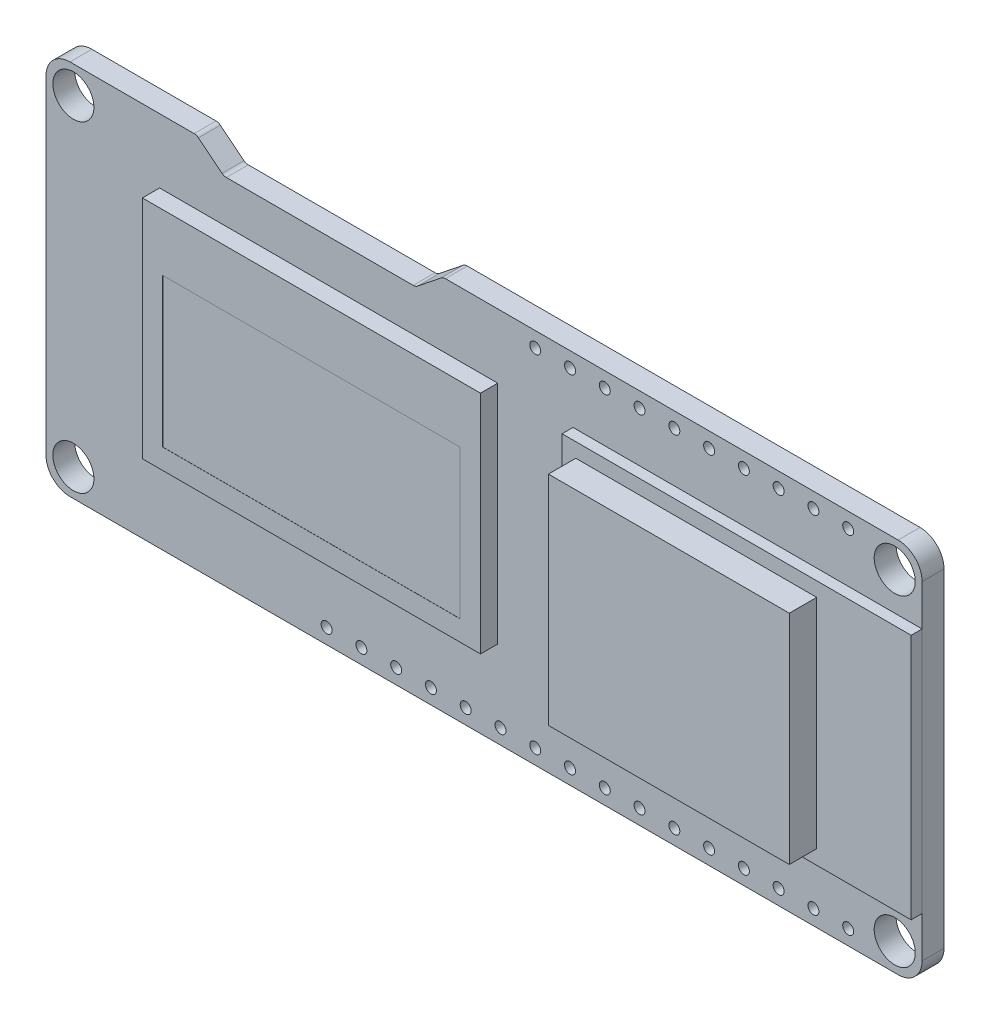
SolidWorks part; units mm, degrees
other "OLED"
other "ESP32"
other "PCB"
ref_plane "Plan de face" through (0, 0, 0) normal (0, 0, 1) x (1, 0, 0)
ref_plane "Plan de dessus" through (0, 0, 0) normal (0, 1, 0) x (1, 0, 0)
ref_plane "Plan de droite" through (0, 0, 0) normal (1, 0, 0) x (0, 0, -1)
sketch "Esquisse1" plane through (0, 0, 0) normal (0, 0, 1) x (1, 0, 0)
  line L0 (-20.863, 13.6404) -> (-19.137, 12.2596)
  line L1 (-30.25, -13.75) -> (30.25, -13.75)
  line L2 (-32, -12) -> (-32, 12)
  line L3 (-30.25, 13.75) -> (-21.1754, 13.75)
  line L4 (32, -12) -> (32, 12)
  line L5 (-32, -13.75) -> (32, 13.75) construction
  line L6 (-32, 13.75) -> (32, -13.75) construction
  line L7 (-30, -11.75) -> (30, -11.75) construction
  line L8 (-30, -11.75) -> (-30, 11.75) construction
  line L9 (-30, 11.75) -> (30, 11.75) construction
  line L10 (30, -11.75) -> (30, 11.75) construction
  line L11 (-30, -11.75) -> (30, 11.75) construction
  line L12 (-30, 11.75) -> (30, -11.75) construction
  line L13 (-18.8246, 12.15) -> (-5.1754, 12.15)
  line L14 (-4.863, 12.2596) -> (-3.137, 13.6404)
  line L15 (-21, 13.75) -> (-3, 13.75) construction
  line L16 (-2.8246, 13.75) -> (30.25, 13.75)
  line L17 (32, 0) -> (0, 0) construction
  arc A0 (30.25, -13.75) -> (32, -12) centre (30.25, -12) ccw
  arc A1 (-30.25, -13.75) -> (-32, -12) centre (-30.25, -12) cw
  arc A2 (-32, 12) -> (-30.25, 13.75) centre (-30.25, 12) cw
  arc A3 (30.25, 13.75) -> (32, 12) centre (30.25, 12) cw
  circle A4 centre (30, 11.75) radius 1.5
  circle A5 centre (30, -11.75) radius 1.5
  circle A6 centre (-30, -11.75) radius 1.5
  circle A7 centre (-30, 11.75) radius 1.5
  arc A8 (-2.8246, 13.75) -> (-3.137, 13.6404) centre (-2.8246, 13.25) ccw
  arc A9 (-4.863, 12.2596) -> (-5.1754, 12.15) centre (-5.1754, 12.65) cw
  arc A10 (-19.137, 12.2596) -> (-18.8246, 12.15) centre (-18.8246, 12.65) ccw
  arc A11 (-20.863, 13.6404) -> (-21.1754, 13.75) centre (-21.1754, 13.25) ccw
  circle A12 centre (26.6, 12.65) radius 0.4
  circle A13 centre (24.06, 12.65) radius 0.4
  circle A14 centre (21.52, 12.65) radius 0.4
  circle A15 centre (18.98, 12.65) radius 0.4
  circle A16 centre (16.44, 12.65) radius 0.4
  circle A17 centre (13.9, 12.65) radius 0.4
  circle A18 centre (11.36, 12.65) radius 0.4
  circle A19 centre (8.82, 12.65) radius 0.4
  circle A20 centre (6.28, 12.65) radius 0.4
  circle A21 centre (3.74, 12.65) radius 0.4
  circle A22 centre (26.6, -12.65) radius 0.4
  circle A23 centre (24.06, -12.65) radius 0.4
  circle A24 centre (21.52, -12.65) radius 0.4
  circle A25 centre (18.98, -12.65) radius 0.4
  circle A26 centre (16.44, -12.65) radius 0.4
  circle A27 centre (13.9, -12.65) radius 0.4
  circle A28 centre (11.36, -12.65) radius 0.4
  circle A29 centre (8.82, -12.65) radius 0.4
  circle A30 centre (6.28, -12.65) radius 0.4
  circle A31 centre (3.74, -12.65) radius 0.4
  circle A32 centre (1.2, -12.65) radius 0.4
  circle A33 centre (-1.34, -12.65) radius 0.4
  circle A34 centre (-3.88, -12.65) radius 0.4
  circle A35 centre (-6.42, -12.65) radius 0.4
  circle A36 centre (-8.96, -12.65) radius 0.4
  circle A37 centre (-11.5, -12.65) radius 0.4
  point P0 (0, 0)
  point P18 (0, 0)
  point P27 (-19, 13.75)
  point P28 (-5, 13.75)
  point P29 (-21, 13.75)
  point P30 (-3, 13.75)
  point P31 (-19, 12.15)
  point P33 (-5, 12.15)
  point P42 (-5, 12.15)
  point P45 (-19, 12.15)
  dimension "D3" = 1.75
  dimension "D6" = 3
  dimension "D12" = 0.5
  dimension "D13" = 5.4
  dimension "D15" = 0.8
  dimension "D1" = 27.5
  dimension "D2" = 64
  dimension "D4" = 2
  dimension "D5" = 2
  dimension "D7" = 13
  dimension "D8" = 2
  dimension "D9" = 2
  dimension "D10" = 14
  dimension "D11" = 1.6
  dimension "D14" = 1.1
  dimension "D17" = 16
  dimension "D16" = 10
extrude "Boss.-Extru.1" add sketch "Esquisse1" against normal blind 1.6
sketch "Esquisse2" plane through (0, 0, 0) normal (0, 0, 1) x (1, 0, 0)
  line L0 (32, -12) -> (32, 12) construction
  line L1 (32, 9) -> (6.5, 9)
  line L2 (32, 9) -> (32, -9)
  line L3 (32, -9) -> (6.5, -9)
  line L4 (6.5, 9) -> (6.5, -9)
  point P7 (32, 0)
  dimension "D1" = 18
  dimension "D2" = 25.5
extrude "Boss.-Extru.2" add sketch "Esquisse2" along normal blind 0.8 separate body
sketch "Esquisse3" plane through (0, 0, 0.8) normal (0, 0, 1) x (1, 0, 0)
  line L0 (6.5, 9) -> (6.5, -9) construction
  line L1 (7.5, 7.95) -> (25.1, 7.95)
  line L2 (7.5, 7.95) -> (7.5, -7.95)
  line L3 (7.5, -7.95) -> (25.1, -7.95)
  line L4 (25.1, 7.95) -> (25.1, -7.95)
  line L5 (6.5, 0) -> (7.5, 0) construction
  point P6 (6.5, 0)
  dimension "D1" = 1
  dimension "D2" = 15.9
  dimension "D3" = 17.6
extrude "Boss.-Extru.3" add sketch "Esquisse3" along normal blind 2
sketch "Esquisse4" plane through (0, 0, 0) normal (0, 0, 1) x (1, 0, 0)
  line L0 (-32, 12) -> (-32, -12) construction
  line L1 (-23.7, 9.05) -> (1, 9.05)
  line L2 (-23.7, 9.05) -> (-23.7, -7.45)
  line L3 (-23.7, -7.45) -> (1, -7.45)
  line L4 (1, 9.05) -> (1, -7.45)
  line L6 (-21.1754, 13.75) -> (-30.25, 13.75) construction
  dimension "D1" = 16.5
  dimension "D2" = 24.7
  dimension "D3" = 4.7
  dimension "D4" = 8.3
extrude "Boss.-Extru.4" add sketch "Esquisse4" along normal blind 1.26 separate body
sketch "Esquisse5" plane through (0, 0, 1.26) normal (0, 0, 1) x (1, 0, 0)
  line L0 (-22.22, 4.89) -> (-23.7, 4.89) construction
  line L1 (-22.22, 4.89) -> (-0.48, 4.89)
  line L2 (-22.22, 4.89) -> (-22.22, -5.97)
  line L3 (-22.22, -5.97) -> (-0.48, -5.97)
  line L4 (-0.48, 4.89) -> (-0.48, -5.97)
  line L5 (-23.7, 9.05) -> (-23.7, -7.45) construction
  line L6 (-22.22, -5.97) -> (-22.22, -7.45) construction
  line L8 (-0.48, 4.89) -> (1, 4.89) construction
  line L9 (1, -7.45) -> (1, 9.05) construction
  line L10 (-23.7, -7.45) -> (1, -7.45) construction
  dimension "D1" = 21.74
  dimension "D2" = 10.86
extrude "Enlèv. mat.-Extru.1" cut sketch "Esquisse5" against normal blind 0.1
other "Déplacer la face2" face at (-11.35, -0.54, 1.16) offset 0.09 parameters "D1"=0.09
sketch "Esquisse7" plane through (0, 0, -1.6) normal (0, 0, -1) x (-1, 0, 0)
  line L0 (32, 12) -> (32, -12) construction
  line L1 (32, -8.55) -> (26.2, -8.55)
  line L2 (32, -8.55) -> (32, -0.55)
  line L3 (32, -0.55) -> (26.2, -0.55)
  line L4 (26.2, -8.55) -> (26.2, -0.55)
  line L5 (30.25, -13.75) -> (-30.25, -13.75) construction
  point P6 (26.2, -4.55)
  dimension "D1" = 8
  dimension "D2" = 5.8
  dimension "D3" = 5.2
extrude "Boss.-Extru.5" add sketch "Esquisse7" along normal blind 2.6
sketch "Esquisse8" plane through (-32, 0, 0) normal (-1, 0, 0) x (0, 0, 1)
  line L0 (-4.2, -8.55) -> (-1.6, -8.55) construction
  line L1 (-4.2, -0.55) -> (-1.4, -0.55)
  line L2 (-4.2, -0.55) -> (-4.2, -8.55)
  line L3 (-4.2, -8.55) -> (-1.4, -8.55)
  line L4 (-1.4, -0.55) -> (-1.4, -8.55)
  dimension "D1" = 2.8
extrude "Boss.-Extru.6" add sketch "Esquisse8" along normal blind 0.8
fillet "Congé1" radius 0.66 2 edges at (-29.5, -0.55, -4.2) (-29.5, -8.55, -4.2)
chamfer "Chanfrein1" distance 1 angle 45 2 edges at (-32.4, -0.55, -1.4) (-32.4, -8.55, -1.4)
sketch "Esquisse9" plane through (-32.8, 0, 0) normal (-1, 0, 0) x (0, 0, 1)
  line L6 (-3.05, -4.55) -> (-3.87, -4.55) construction
  line L7 (-3.05, -2.55) -> (-2.55, -2.55)
  line L8 (-3.05, -2.55) -> (-3.05, -6.55)
  line L9 (-3.05, -6.55) -> (-2.55, -6.55)
  line L10 (-2.55, -2.55) -> (-2.55, -6.55)
  line L11 (-2.55, -4.55) -> (-1.73, -4.55) construction
  line L12 (-1.73, -7.4133) -> (-1.73, -1.6867)
  line L13 (-1.73, -1.6867) -> (-2.5367, -0.88)
  line L14 (-2.5367, -0.88) -> (-3.54, -0.88)
  line L15 (-3.87, -1.21) -> (-3.87, -7.89)
  line L16 (-3.54, -8.22) -> (-2.5367, -8.22)
  line L17 (-2.5367, -8.22) -> (-1.73, -7.4133)
  line L18 (-1.73, -7.4133) -> (-1.73, -1.6867)
  line L19 (-1.73, -1.6867) -> (-2.5367, -0.88)
  line L20 (-2.5367, -0.88) -> (-3.54, -0.88)
  line L21 (-3.87, -1.21) -> (-3.87, -7.89)
  line L22 (-3.54, -8.22) -> (-2.5367, -8.22)
  line L23 (-2.5367, -8.22) -> (-1.73, -7.4133)
  arc A4 (-3.54, -0.88) -> (-3.87, -1.21) centre (-3.54, -1.21) ccw
  arc A5 (-3.87, -7.89) -> (-3.54, -8.22) centre (-3.54, -7.89) ccw
  arc A6 (-3.54, -0.88) -> (-3.87, -1.21) centre (-3.54, -1.21) ccw
  arc A7 (-3.87, -7.89) -> (-3.54, -8.22) centre (-3.54, -7.89) ccw
  dimension "D2" = 0.5
  dimension "D3" = 4
  dimension "D1" = 0.33
extrude "Enlèv. mat.-Extru.2" cut sketch "Esquisse9" against normal blind 5
sketch "Esquisse10" plane through (0, 0, -1.6) normal (0, 0, -1) x (-1, 0, 0)
  line L0 (32, 12) -> (32, -1.35) construction
  line L1 (28.4, 7.55) -> (31.4, 7.55)
  line L2 (28.4, 7.55) -> (28.4, 3.55)
  line L3 (28.4, 3.55) -> (31.4, 3.55)
  line L4 (31.4, 7.55) -> (31.4, 3.55)
  line L5 (21.1754, 13.75) -> (30.25, 13.75) construction
  line L6 (24.1, 7.55) -> (24.1, 3.55)
  line L7 (24.1, 7.55) -> (27.1, 7.55)
  line L8 (27.1, 7.55) -> (27.1, 3.55)
  line L9 (24.1, 3.55) -> (27.1, 3.55)
  dimension "D1" = 4
  dimension "D2" = 3
  dimension "D3" = 0.6
  dimension "D4" = 6.2
  dimension "D5" = 2
extrude "Boss.-Extru.7" add sketch "Esquisse10" along normal blind 1.8
sketch "Esquisse11" plane through (0, 0, -3.4) normal (0, 0, -1) x (-1, 0, 0)
  line L0 (31.4, 7.55) -> (28.4, 3.55) construction
  line L1 (27.1, 7.55) -> (24.1, 3.55) construction
  circle A0 centre (25.6, 5.55) radius 0.9
  circle A1 centre (29.9, 5.55) radius 0.9
  dimension "D1" = 1.8
extrude "Boss.-Extru.8" add sketch "Esquisse11" along normal blind 0.5
sketch "Esquisse12" plane through (0, 0, -1.6) normal (0, 0, -1) x (-1, 0, 0)
  line L0 (-3.5, 8.05) -> (-3.5, -11.25)
  line L2 (32, 12) -> (32, -1.35) construction
  line L3 (27.1, 7.55) -> (24.1, 7.55) construction
  line L4 (-3.5, 8.05) -> (22.7644, 8.05)
  line L5 (22.7644, 8.05) -> (22.7644, 2.05)
  line L6 (22.7644, 2.05) -> (24.4, 2.05)
  line L7 (24.4, 2.05) -> (24.4, -9.75)
  line L8 (24.4, -9.75) -> (26, -9.75)
  line L9 (26, -9.75) -> (26, -13.75)
  line L10 (30.25, -13.75) -> (-30.25, -13.75) construction
  line L11 (26, -13.75) -> (14.4, -13.75)
  line L12 (14.4, -13.75) -> (14.4, -11.25)
  line L13 (14.4, -11.25) -> (-3.5, -11.25)
  line L14 (26.2, -1.35) -> (26.2, -7.75) construction
  line L15 (32, -7.75) -> (32, -12) construction
  line L16 (-32, -12) -> (-32, 12) construction
  line L17 (-25.5, 7.05) -> (-14, 7.05)
  line L18 (-25.5, 7.05) -> (-25.5, -3.95)
  line L19 (-25.5, -3.95) -> (-14, -3.95)
  line L20 (-14, 7.05) -> (-14, -3.95)
  line L21 (-30.25, 13.75) -> (2.8246, 13.75) construction
  circle A0 centre (11.5, -12.65) radius 0.4 construction
  point P20 (26.2, -4.55)
  dimension "D1" = 35.5
  dimension "D2" = 0.5
  dimension "D3" = 6
  dimension "D4" = 1.8
  dimension "D5" = 4
  dimension "D6" = 6
  dimension "D7" = 2.9
  dimension "D8" = 2.5
  dimension "D9" = 18
  dimension "D10" = 6.7
  dimension "D11" = 9.8
  dimension "D12" = 6.5
extrude "Boss.-Extru.9" add sketch "Esquisse12" along normal blind 2 separate body
